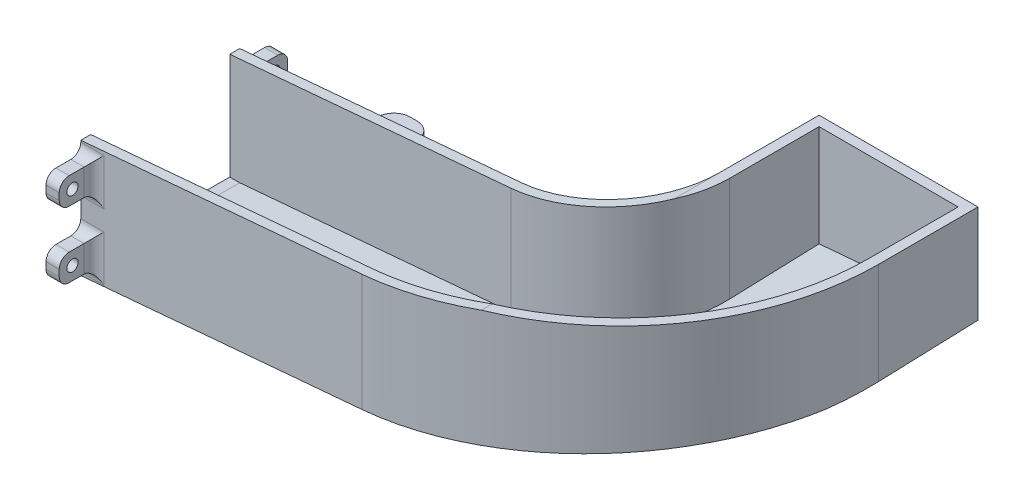
SolidWorks part; units mm, degrees
ref_plane "Front Plane" through (0, 0, 0) normal (0, 0, 1) x (1, 0, 0)
ref_plane "Top Plane" through (0, 0, 0) normal (0, 1, 0) x (1, 0, 0)
ref_plane "Right Plane" through (0, 0, 0) normal (1, 0, 0) x (0, 0, -1)
sketch "Sketch2" plane through (0, 0, 0) normal (0, 1, 0) x (1, 0, 0)
  line L1 (0, 0) -> (85, 0)
  line L2 (0, 0) -> (0, 48)
  line L3 (0, 48) -> (85, 48)
  line L8 (115, 78) -> (115, 108)
  line L9 (115, 108) -> (163, 108)
  line L10 (163, 78) -> (163, 108)
  arc A1 (85, 48) -> (115, 78) centre (85, 78) ccw
  arc A2 (85, 0) -> (163, 78) centre (85, 78) ccw
  point P9 (0, 0)
  point P11 (0, 0)
  dimension "D1" = 48
  dimension "D5" = 30
  dimension "D2" = 85
  dimension "D3" = 48
  dimension "D4" = 115
extrude "Boss-Extrude1" add sketch "Sketch2" along normal blind 50
sketch "Sketch3" plane through (0, 0, 0) normal (0, 0, 1) x (1, 0, 0)
  line L0 (0, 0) -> (200, 17.4977)
  line L2 (0, 50) -> (0, 0) construction
  line L3 (200, 0) -> (200, 17.4977)
  line L5 (0, 0) -> (200, 0)
  line L7 (0, 35.39) -> (0, 50)
  line L8 (0, 50) -> (200, 50)
  line L9 (0, 50) -> (85, 50) construction
  line L11 (163, 50) -> (85, 50) construction
  line L12 (0, 35.39) -> (115, 45.4512)
  line L13 (115, 45.4512) -> (200, 45.4512)
  line L14 (200, 45.4512) -> (200, 50)
  point P4 (140.9944, 57.1439)
  point P14 (154.6463, 60)
  point P17 (180.8999, 60)
  point P18 (132.5245, 57.8644)
  point P21 (113.8292, 56.2288)
  point P23 (0, 0)
  dimension "D1" = 35.39
  dimension "D2" = 200
  dimension "D3" = 5
extrude "Cut-Extrude1" cut sketch "Sketch3" against normal through all
sketch "Sketch18" plane through (163, 0, 0) normal (-1, 0, 0) x (0, 0, 1)
  line L0 (-123, 8.2607) -> (-53, 8.2607)
  line L4 (-123, 8.2607) -> (-123, 16.3451)
  line L5 (-48, 35.39) -> (-48, 0) construction
  line L6 (-78, 14.2607) -> (-108, 14.2607) construction
  line L7 (-53, 8.2607) -> (-53, 13.9006)
  line L8 (-53, 13.9006) -> (-123, 16.3451)
  ellipse E3 centre (-78, 7.4365) end of major axis (0, 7.4365) minor radius 6.8241 (0, 7.4365) -> (-78, 14.2607) ccw construction
  dimension "D1" = 2
  dimension "D2" = 70
  dimension "D3" = 6
  dimension "D4" = 5
extrude "Cut-Extrude9" cut sketch "Sketch18" along direction (-0.9962, -0.0872, 0) on the side against the normal blind 55 and the other way blind 55
shell "Shell4" thickness 3 removed face at (67.7517, 41.3175, -28.7169) removed face at (136.38, 45.4512, -74.1467)
sketch "Sketch15" plane through (3, 0, 0) normal (1, 0, 0) x (0, 0, -1)
  line L4 (45, 35.6525) -> (3, 35.6525)
  line L5 (45, 35.6525) -> (3, 35.6525)
  line L8 (3, 35.6525) -> (3, 3.2739)
  line L9 (3, 3.2739) -> (45, 3.2739)
  line L10 (45, 3.2739) -> (45, 35.6525)
  line L12 (3, 35.6525) -> (3, 3.2739)
  line L13 (3, 3.2739) -> (45, 3.2739)
  line L14 (45, 3.2739) -> (45, 35.6525)
  dimension "D1" = 0
extrude "Cut-Extrude8" cut sketch "Sketch15" against normal up to surface (3 mm away) up to face at (0, 17.695, -24)
sketch "Sketch16" plane through (0, 0, 0) normal (-1, 0, 0) x (0, 0, 1)
  line L1 (-1.5, 31.89) -> (10.5, 31.89)
  line L2 (-1.5, 31.89) -> (-1.5, 23.89)
  line L3 (-1.5, 23.89) -> (10.5, 23.89)
  line L4 (10.5, 31.89) -> (10.5, 23.89)
  line L5 (0, 35.39) -> (0, 0) construction
  line L7 (-3, 35.39) -> (0, 35.39) construction
  line L8 (-1.5, 11.89) -> (10.5, 11.89)
  line L13 (-1.5, 11.89) -> (-1.5, 3.89)
  line L14 (-1.5, 3.89) -> (10.5, 3.89)
  line L15 (10.5, 11.89) -> (10.5, 3.89)
  line L16 (-24, 0) -> (-24, 60) construction
  line L17 (-48, 0) -> (0, 0) construction
  line L18 (-58.5, 11.89) -> (-58.5, 3.89)
  line L19 (-46.5, 3.89) -> (-58.5, 3.89)
  line L20 (-46.5, 11.89) -> (-46.5, 3.89)
  line L21 (-46.5, 11.89) -> (-58.5, 11.89)
  line L22 (-58.5, 31.89) -> (-58.5, 23.89)
  line L23 (-46.5, 23.89) -> (-58.5, 23.89)
  line L24 (-46.5, 31.89) -> (-46.5, 23.89)
  line L25 (-46.5, 31.89) -> (-58.5, 31.89)
  circle A0 centre (6.5, 27.89) radius 1.7
  circle A2 centre (6.5, 7.89) radius 1.7
  circle A3 centre (-54.5, 7.89) radius 1.7
  circle A4 centre (-54.5, 27.89) radius 1.7
  point P10 (10.5, 27.89)
  dimension "D1" = 3.4
  dimension "D2" = 8
  dimension "D3" = 4
  dimension "D4" = 1.5
  dimension "D5" = 3.5
  dimension "D6" = 8
  dimension "D7" = 2
  dimension "D8" = 20
  dimension "D9" = 60
extrude "Boss-Extrude2" add sketch "Sketch16" against normal blind 4
fillet "Fillet1" radius 3 20 edges at (2, 3.89, 10.5) (2, 3.89, 0) (4, 7.89, 0) (2, 11.89, 10.5) (2, 11.89, 0) (2, 23.89, 10.5) (2, 23.89, 0) (4, 27.89, 0) (2, 31.89, 0) (2, 31.89, 10.5) (2, 11.89, -58.5) (2, 3.89, -58.5) (2, 3.89, -48) (4, 7.89, -48) (2, 11.89, -48) (4, 27.89, -48) (2, 23.89, -48) (2, 23.89, -58.5) (2, 31.89, -48) (2, 31.89, -58.5)
sketch "Sketch19" plane through (0, 45.4512, 0) normal (0, 1, 0) x (1, 0, 0)
  line L0 (115, 108) -> (163, 108) construction
  line L2 (115, 108) -> (115, 78) construction
  line L3 (115, 90.77) -> (91.77, 90.77)
  line L4 (115, 90.77) -> (115, 78.77)
  line L5 (115, 78.77) -> (91.77, 78.77)
  line L6 (91.77, 90.77) -> (91.77, 78.77)
  line L7 (0, 48) -> (85, 48) construction
  line L8 (75.77, 48) -> (87.77, 48)
  line L9 (75.77, 48) -> (75.77, 72.77)
  line L10 (75.77, 72.77) -> (87.77, 72.77)
  line L11 (87.77, 48) -> (87.77, 72.77)
  line L29 (21.77, 48) -> (33.77, 48)
  line L34 (21.77, 48) -> (21.77, 72.77)
  line L35 (21.77, 72.77) -> (33.77, 72.77)
  line L36 (33.77, 48) -> (33.77, 72.77)
  circle A0 centre (97.77, 84.77) radius 2.2
  circle A1 centre (81.77, 66.77) radius 2.2
  circle A4 centre (27.77, 66.77) radius 2.2
  point P11 (91.77, 84.77)
  point P20 (81.77, 72.77)
  line M10 (115, 108) -> (115, 78)
  dimension "D3" = 4.4
  dimension "D8" = 12
  dimension "D11" = 54
  dimension "D1" = 23.23
  dimension "D2" = 17.23
  dimension "D4" = 12
  dimension "D5" = 6
  dimension "D6" = 41.23
  dimension "D7" = 33.23
  dimension "D9" = 6
  dimension "D10" = 2
extrude "Boss-Extrude3" add sketch "Sketch19" against normal blind 5 from offset 27 contours L34 | L34 | L8 L11 L10 L9 A1 | L3 L6 L5 A0 M10 region at (103.7089, 45.4512, -84.77) region at (81.77, 45.4512, -60.0408) region at (27.77, 45.4512, -60.0408) offset against normal yes
fillet "Fillet6" radius 5 19 edges at (86.3865, 18.4512, -48.0321) (86.3865, 13.4512, -48.0321) (115, 13.4512, -84.77) (115, 15.9512, -90.77) (115, 18.4512, -84.77) (87.77, 15.9512, -48.1282) (80.385, 18.4512, -48) (75.77, 15.9512, -48) (80.385, 13.4512, -48) (27.77, 13.4512, -48) (33.77, 15.9512, -48) (21.77, 15.9512, -48) (27.77, 18.4512, -48) (21.77, 15.9512, -72.77) (33.77, 15.9512, -72.77) (87.77, 15.9512, -72.77) (75.77, 15.9512, -72.77) (91.77, 15.9512, -90.77) (91.77, 15.9512, -78.77)
fillet "Fillet9" radius 0.5 1 edges at (115, 17.0261, -78.77)
